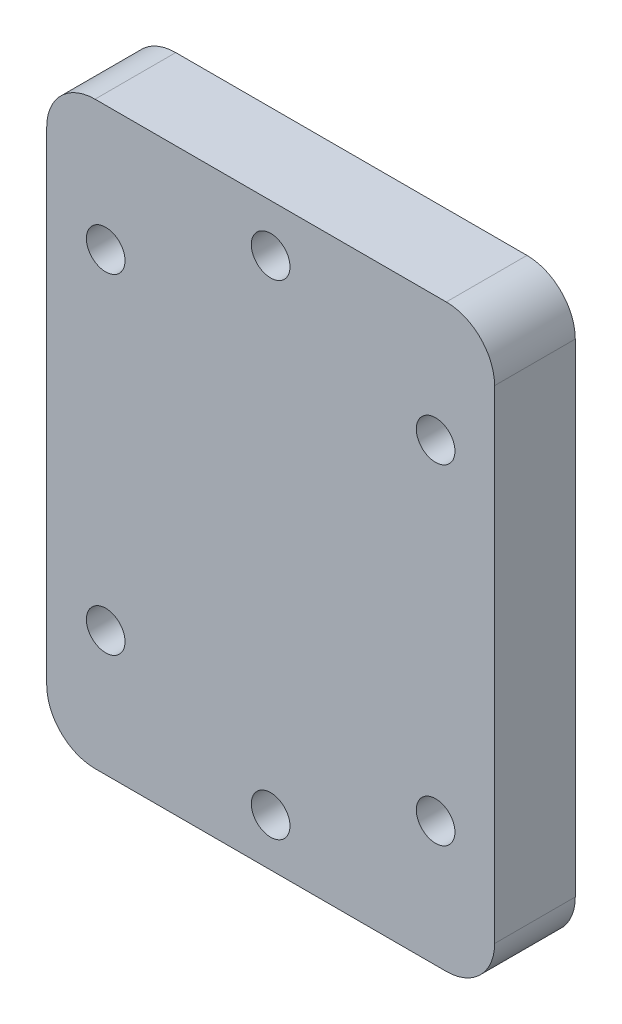
SolidWorks part; units mm, degrees
material "ABS"
ref_plane "X-Y Datum" through (0, 0, 0) normal (0, 0, 1) x (1, 0, 0)
ref_plane "X-Z Datum" through (0, 0, 0) normal (0, 1, 0) x (1, 0, 0)
ref_plane "Y-Z Datum" through (0, 0, 0) normal (1, 0, 0) x (0, 0, -1)
sketch "Sketch1" plane through (0, 0, 0) normal (0, 0, 1) x (1, 0, 0)
  line L0 (0, 30) -> (0, 20.1212) construction
  line L1 (-23.175, 0) -> (23.175, 0) construction
  line L4 (-20, 20) -> (-20, -20) construction
  line L5 (-23.175, -30) -> (23.175, -30)
  line L6 (-23.175, -30) -> (-23.175, 30)
  line L7 (-23.175, 30) -> (23.175, 30)
  line L8 (23.175, -30) -> (23.175, 30)
  line L9 (-23.175, -30) -> (23.175, 30) construction
  line L10 (-23.175, 30) -> (23.175, -30) construction
  line L11 (20, 20) -> (-20, 20) construction
  line L12 (-23.175, 20.1212) -> (23.175, 20.1212) construction
  circle A0 centre (0, 25.0606) radius 2
  circle A1 centre (0, -25.0606) radius 2
  circle A2 centre (17.0711, 17.0711) radius 2 construction
  circle A3 centre (17.0711, -17.0711) radius 2 construction
  circle A4 centre (-17.0711, -17.0711) radius 2 construction
  circle A5 centre (-17.0711, 17.0711) radius 2 construction
  circle A6 centre (17.0711, 17.0711) radius 2
  circle A7 centre (17.0711, -17.0711) radius 2
  circle A8 centre (-17.0711, -17.0711) radius 2
  circle A9 centre (-17.0711, 17.0711) radius 2
  point P2 (0, 0)
  dimension "D3" = 4
  dimension "D1" = 3.175
  dimension "D2" = 10
  dimension "D4" = 4.9394
extrude "Boss-Extrude1" add sketch "Sketch1" against normal blind 6.35 and the other way blind 2 contours L5 L8 L7 L6 A9 A8 A7 A6 A0 A1 region at (0, 0, 0)
sketch "Sketch2" plane through (0, 0, -6.35) normal (0, 0, -1) x (-1, 0, 0)
  line L1 (-15, -15) -> (15, -15)
  line L2 (-15, -15) -> (-15, 15)
  line L3 (-15, 15) -> (15, 15)
  line L4 (15, -15) -> (15, 15)
  line L5 (-15, -15) -> (15, 15) construction
  line L6 (-15, 15) -> (15, -15) construction
  point P0 (0, 0)
  dimension "D1" = 30
  dimension "D2" = 30
extrude "Cut-Extrude1" cut sketch "Sketch2" against normal blind 6.35
sketch "Sketch4" plane through (0, 0, -6.35) normal (0, 0, -1) x (-1, 0, 0)
  circle A0 centre (-17.0711, 17.0711) radius 2
  circle A1 centre (17.0711, 17.0711) radius 2
  circle A2 centre (-17.0711, -17.0711) radius 2
  circle A3 centre (17.0711, -17.0711) radius 2
extrude "Boss-Extrude4" add sketch "Sketch4" against normal blind 0.85
fillet "Fillet1" radius 5 4 edges at (23.175, 30, -2.175) (-23.175, 30, -2.175) (-23.175, -30, -2.175) (23.175, -30, -2.175)
